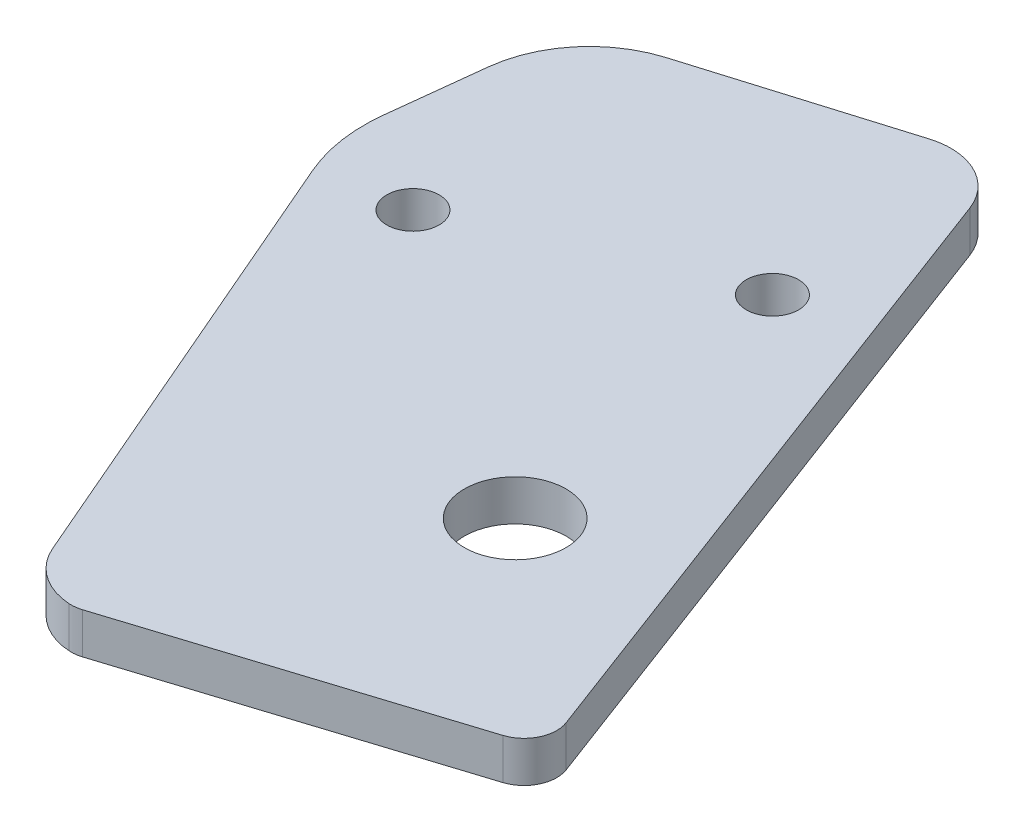
SolidWorks part; units mm, degrees
ref_plane "Front Plane" through (0, 0, 0) normal (0, 0, 1) x (1, 0, 0)
ref_plane "Top Plane" through (0, 0, 0) normal (0, 1, 0) x (1, 0, 0)
ref_plane "Right Plane" through (0, 0, 0) normal (1, 0, 0) x (0, 0, -1)
sketch "Sketch1" plane through (0, 0, 0) normal (0, 1, 0) x (1, 0, 0)
  line L0 (12.7, -6.35) -> (25.4, -6.35)
  line L1 (-12.7, -19.05) -> (12.7, -19.05)
  line L2 (-12.7, -19.05) -> (-12.7, 19.05)
  line L3 (-12.7, 19.05) -> (12.7, 19.05)
  line L4 (12.7, -19.05) -> (12.7, 19.05)
  line L5 (-12.7, -19.05) -> (12.7, 19.05) construction
  line L6 (-12.7, 19.05) -> (12.7, -19.05) construction
  line L7 (25.4, -6.35) -> (25.4, -19.05)
  line L8 (25.4, -19.05) -> (12.7, -19.05)
  point P0 (0, 0)
  dimension "D1" = 25.4
  dimension "D2" = 38.1
  dimension "D3" = 12.7
  dimension "D4" = 12.7
extrude "Boss-Extrude1" add sketch "Sketch1" along normal blind 3.175 contours L1 L4 L3 L2 | L8 L7 L0 L4 region at (19.05, 0, 12.7) region at (0, 0, 0)
sketch "Sketch2" plane through (0, 0, 0) normal (0, -1, 0) x (1, 0, 0)
  line L0 (37.3484, -5.4015) -> (58.4225, -30.0473) construction
  line L1 (58.4225, -30.0473) -> (56.4244, -36.6557) construction
  line L2 (56.4244, -36.6557) -> (28.4937, -28.211) construction
  line L3 (27.672, -14.5925) -> (16.8921, 0.2466) construction
  line L4 (18.9846, 3.1897) -> (28.6818, 0.2578) construction
  line L5 (-33.4925, -38.7551) -> (-34.3249, -31.4398) construction
  line L6 (-33.4148, -25.2954) -> (-18.0647, 10.2749) construction
  line L7 (-1.2058, -33.65) -> (-6.5286, -47.7836) construction
  line L8 (-11.9748, -50.4718) -> (-27.6795, -45.7236) construction
  line L9 (37.3484, -5.4015) -> (58.4225, -30.0473)
  line L10 (58.4225, -30.0473) -> (56.4244, -36.6557)
  line L11 (56.4244, -36.6557) -> (28.4937, -28.211)
  line L12 (27.672, -14.5925) -> (16.8921, 0.2466)
  line L13 (18.9846, 3.1897) -> (28.6818, 0.2578)
  line L14 (-33.4925, -38.7551) -> (-34.3249, -31.4398)
  line L15 (-33.4148, -25.2954) -> (-18.0647, 10.2749)
  line L16 (-1.2058, -33.65) -> (-6.5286, -47.7836)
  line L17 (-11.9748, -50.4718) -> (-27.6795, -45.7236)
  line L18 (-13.3731, 13.4695) -> (19.0101, 3.1818)
  line L20 (-25.2482, -46.4587) -> (-27.4348, -26.2567) construction
  line L21 (-13.0917, -50.1342) -> (-7.7649, -34.5071) construction
  line L22 (-34.9558, -31.5116) -> (-34.1234, -38.8269) construction
  line L23 (-27.8633, -46.3314) -> (-12.1585, -51.0797) construction
  line L24 (-5.9343, -48.0074) -> (-0.6115, -33.8738) construction
  line L25 (-18.6477, 10.5265) -> (-33.9978, -25.0438) construction
  line L26 (-34.9558, -31.5116) -> (-34.1234, -38.8269)
  line L27 (-27.8633, -46.3314) -> (-12.1585, -51.0797)
  line L28 (-5.9343, -48.0074) -> (-0.6115, -33.8738)
  line L29 (-18.6477, 10.5265) -> (-33.9978, -25.0438)
  line L31 (-0.6115, -33.8738) -> (13.9492, 4.7896)
  arc A0 (37.3484, -5.4015) -> (28.6818, 0.2578) centre (23.3524, -17.3692) ccw construction
  arc A1 (27.5335, -25.2281) -> (28.4937, -28.211) centre (29.045, -26.3876) ccw construction
  arc A2 (27.5335, -25.2281) -> (27.672, -14.5925) centre (20.4796, -19.8175) ccw construction
  arc A3 (18.9846, 3.1897) -> (16.8921, 0.2466) centre (18.4333, 1.3662) ccw construction
  arc A4 (-33.4925, -38.7551) -> (-27.6795, -45.7236) centre (-25.2904, -37.8219) ccw construction
  arc A5 (-33.4148, -25.2954) -> (-34.3249, -31.4398) centre (-22.3372, -30.0758) ccw construction
  arc A6 (-14.2611, 12.95) -> (-18.0647, 10.2749) centre (-13.9835, 8.5137) ccw construction
  arc A7 (-13.2163, 9.3838) -> (-14.2611, 12.95) centre (-14.1421, 11.0487) ccw construction
  arc A8 (-13.2163, 9.3838) -> (-2.9671, -31.0738) centre (-2.7239, -9.4851) ccw construction
  arc A9 (-1.2058, -33.65) -> (-2.9671, -31.0738) centre (-2.9886, -32.9786) ccw construction
  arc A10 (-11.9748, -50.4718) -> (-6.5286, -47.7836) centre (-10.6883, -46.2171) ccw construction
  arc A11 (37.3484, -5.4015) -> (28.6818, 0.2578) centre (23.3524, -17.3692) ccw
  arc A12 (27.5335, -25.2281) -> (28.4937, -28.211) centre (29.045, -26.3876) ccw
  arc A13 (27.5335, -25.2281) -> (27.672, -14.5925) centre (20.4796, -19.8175) ccw
  arc A14 (18.9846, 3.1897) -> (16.8921, 0.2466) centre (18.4333, 1.3662) ccw
  arc A15 (-33.4925, -38.7551) -> (-27.6795, -45.7236) centre (-25.2904, -37.8219) ccw
  arc A16 (-33.4148, -25.2954) -> (-34.3249, -31.4398) centre (-22.3372, -30.0758) ccw
  arc A17 (-14.2611, 12.95) -> (-18.0647, 10.2749) centre (-13.9835, 8.5137) ccw
  arc A18 (-13.2163, 9.3838) -> (-14.2611, 12.95) centre (-14.1421, 11.0487) ccw
  arc A19 (-13.2163, 9.3838) -> (-2.9671, -31.0738) centre (-2.7239, -9.4851) ccw
  arc A20 (-1.2058, -33.65) -> (-2.9671, -31.0738) centre (-2.9886, -32.9786) ccw
  arc A21 (-11.9748, -50.4718) -> (-6.5286, -47.7836) centre (-10.6883, -46.2171) ccw
  circle A22 centre (-2.7239, -9.4851) radius 3.95
  circle A23 centre (-7.7649, -34.5071) radius 2.032
  circle A24 centre (-27.4348, -26.2567) radius 2.032
  arc A25 (-34.1234, -38.8269) -> (-27.8633, -46.3314) centre (-25.2904, -37.8219) ccw construction
  arc A26 (-12.1585, -51.0797) -> (-5.9343, -48.0074) centre (-10.6883, -46.2171) ccw construction
  arc A27 (-0.6115, -33.8738) -> (-2.96, -30.4388) centre (-2.9886, -32.9786) ccw construction
  arc A28 (-12.9077, 8.8289) -> (-14.3007, 13.5838) centre (-14.1421, 11.0487) ccw construction
  arc A29 (-14.3007, 13.5838) -> (-18.6477, 10.5265) centre (-13.9835, 8.5137) ccw construction
  arc A30 (-33.9978, -25.0438) -> (-34.9558, -31.5116) centre (-22.3372, -30.0758) ccw construction
  arc A31 (-34.1234, -38.8269) -> (-27.8633, -46.3314) centre (-25.2904, -37.8219) ccw
  arc A32 (-12.1585, -51.0797) -> (-5.9343, -48.0074) centre (-10.6883, -46.2171) ccw
  arc A33 (-0.6115, -33.8738) -> (-2.96, -30.4388) centre (-2.9886, -32.9786) ccw
  arc A34 (-12.9077, 8.8289) -> (-14.3007, 13.5838) centre (-14.1421, 11.0487) ccw
  arc A35 (-14.3007, 13.5838) -> (-18.6477, 10.5265) centre (-13.9835, 8.5137) ccw
  arc A36 (-33.9978, -25.0438) -> (-34.9558, -31.5116) centre (-22.3372, -30.0758) ccw
  line M1 (25.4, 19.05) -> (-12.7, 19.05)
  line M2 (-12.7, 19.05) -> (-12.7, -19.05)
  line M3 (-12.7, -19.05) -> (12.7, -19.05)
  line M4 (12.7, -19.05) -> (12.7, 6.35)
  line M5 (12.7, 6.35) -> (25.4, 6.35)
  line M6 (25.4, 6.35) -> (25.4, 19.05)
  dimension "D1" = 7.9
  dimension "D8" = 4.064
  dimension "D2" = 15.24
  dimension "D3" = 16.51
  dimension "D4" = 20.32
  dimension "D5" = 2.54
  dimension "D6" = 67
  dimension "D7" = 92
extrude "Boss-Extrude2" add sketch "Sketch2" against normal blind 3.175 contours L17 A21 L16 A20 A19 A17 L15 A16 L14 A15 M3 M2 | A19 M2 | A20 A19 M3 | L29 A36 L26 A31 L27 A32 L28 A33 A20 L16 A21 L17 A15 L14 A16 L15 A17 A18 A34 A35 M2 | A34 L18 M2 | L31 L18 M4 M5 region at (13.1164, 0, 3.8162) region at (-12.865, 0, 13.2738) region at (-13.8893, 0, -16.3603) region at (-19.8862, 0, -32.0856)
extrude "Cut-Extrude1" cut sketch "Sketch2<3>" against normal through all contours L18 M2 M5 M6 M1 | L31 M3 M4 | A22 region at (8.5325, 0, 13.4044) region at (10.1237, 0, -12.2091) region at (-2.7239, 0, -9.4851)
sketch "Sketch2<3>" plane through (0, 0, 0) normal (0, -1, 0) x (1, 0, 0) same geometry as "Sketch2"
fillet "Fillet1" radius 2.54 1 edges at (13.9492, 1.5875, 4.7896)
